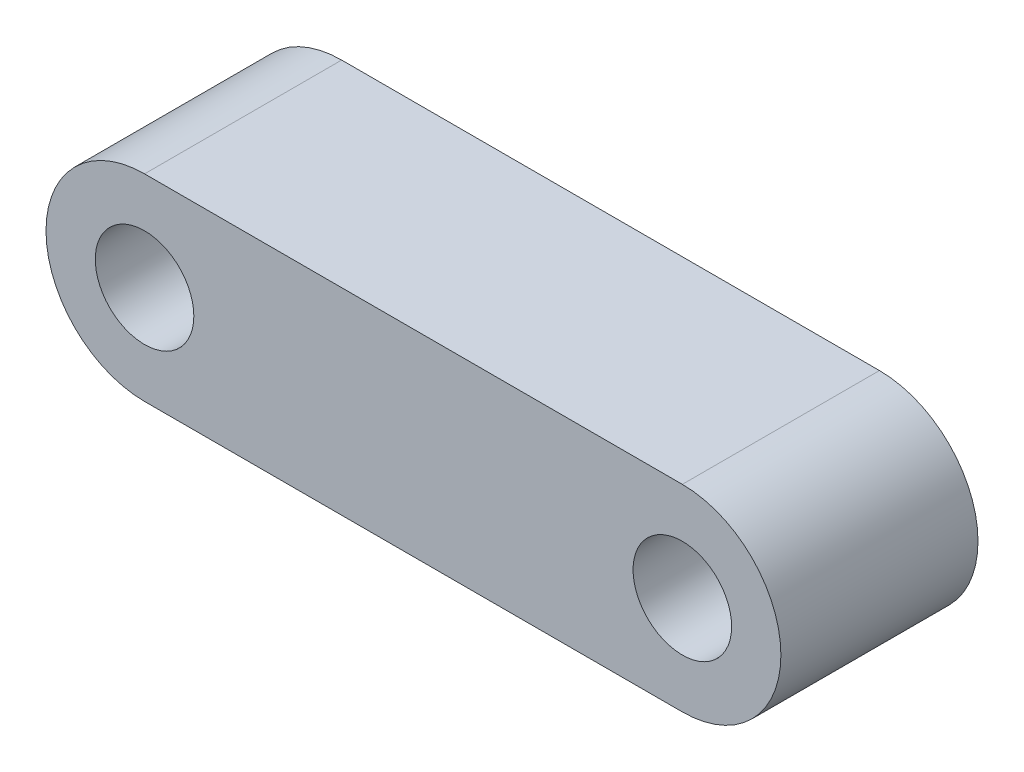
SolidWorks part; units mm, degrees
ref_plane "Plan de face" through (0, 0, 0) normal (0, 0, 1) x (1, 0, 0)
ref_plane "Plan de dessus" through (0, 0, 0) normal (0, 1, 0) x (1, 0, 0)
ref_plane "Plan de droite" through (0, 0, 0) normal (1, 0, 0) x (0, 0, -1)
sketch "Esquisse1" plane through (0, 0, 0) normal (0, 0, 1) x (1, 0, 0)
  line L0 (0, 0) -> (16.37, 0) construction
  line L1 (0, 3) -> (16.37, 3)
  line L2 (0, -3) -> (16.37, -3)
  arc A0 (0, 3) -> (0, -3) centre (0, 0) ccw
  arc A1 (16.37, -3) -> (16.37, 3) centre (16.37, 0) ccw
  circle A2 centre (0, 0) radius 1.5
  circle A3 centre (16.37, 0) radius 1.5
  point P3 (8.185, 0)
  dimension "D1" = 3
  dimension "D2" = 6
  dimension "D3" = 16.37
extrude "Boss.-Extru.1" add sketch "Esquisse1" along normal blind 3 and the other way blind 3
sketch "Esquisse2" plane through (0, 0, 0) normal (0, 0, 1) x (1, 0, 0)
  point P0 (0, 0)
  point P1 (16.37, 0)
